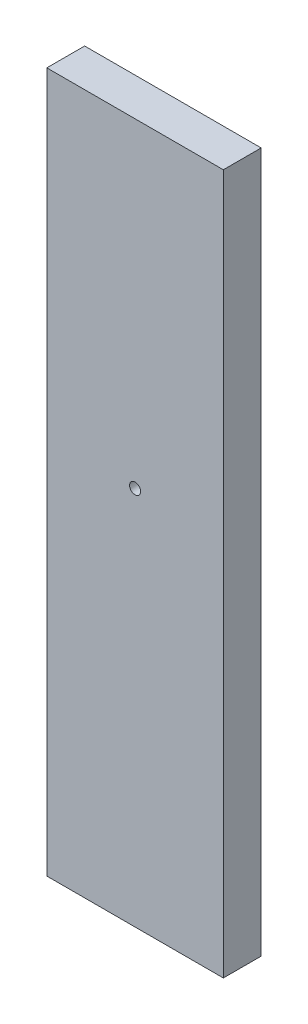
SolidWorks part; units mm, degrees
ref_plane "Front Plane" through (0, 0, 0) normal (0, 0, 1) x (1, 0, 0)
ref_plane "Top Plane" through (0, 0, 0) normal (0, 1, 0) x (1, 0, 0)
ref_plane "Right Plane" through (0, 0, 0) normal (1, 0, 0) x (0, 0, -1)
sketch "Sketch1" plane through (0, 0, 0) normal (0, 1, 0) x (1, 0, 0)
  line L1 (0, 0) -> (88.9, 0)
  line L2 (0, 0) -> (0, 19.05)
  line L3 (0, 19.05) -> (88.9, 19.05)
  line L4 (88.9, 0) -> (88.9, 19.05)
  dimension "D1" = 19.05
  dimension "D2" = 88.9
extrude "Boss-Extrude1" add sketch "Sketch1" along normal blind 352.522
sketch "Sketch2" plane through (0, 0, 0) normal (0, 0, 1) x (1, 0, 0)
  line L0 (44.45, 352.522) -> (44.45, 191.3014) construction
  line L1 (0, 352.522) -> (88.9, 352.522) construction
  line L2 (-349.25, 239.6416) -> (44.45, 191.3014) construction
  line L3 (-349.25, 239.6416) -> (-39.4224, 239.6416) construction
  circle A0 centre (44.45, 191.3014) radius 2.7781
  circle A1 centre (-349.25, 239.6416) radius 2.7781 construction
  circle A2 centre (-349.25, 239.6416) radius 2.7781 construction
  dimension "D1" = 5.5562
  dimension "D2" = 7
extrude "Cut-Extrude1" cut sketch "Sketch2" against normal through all
equation "\"DROPANGLE\"= 10"
